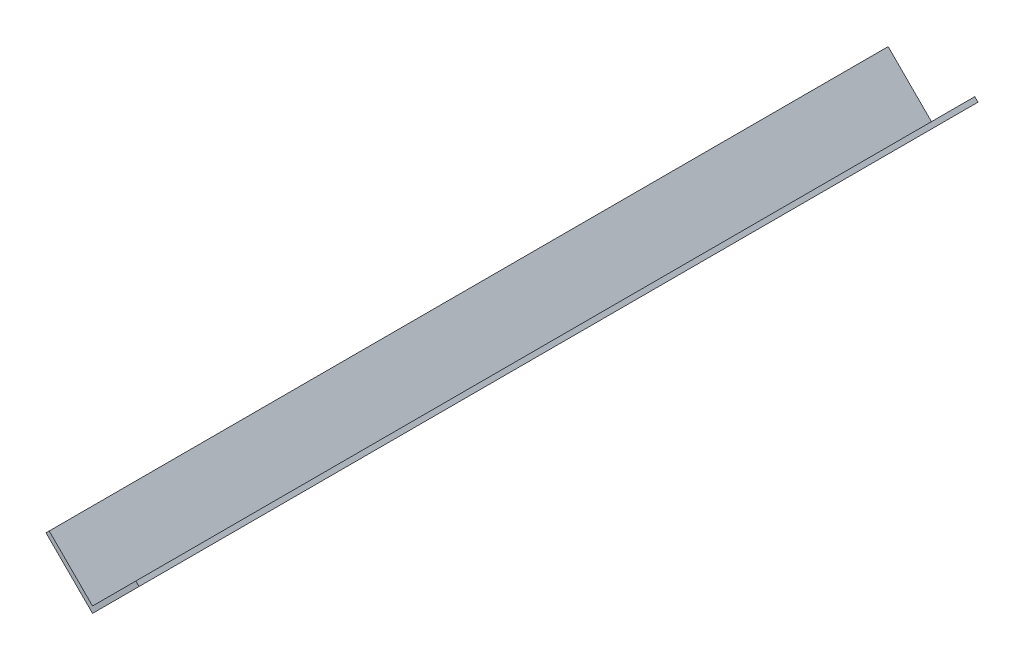
SolidWorks part; units mm, degrees
material "6061 Alloy"
ref_plane "Front Plane" through (0, 0, 0) normal (0, 0, 1) x (1, 0, 0)
ref_plane "Top Plane" through (0, 0, 0) normal (0, 1, 0) x (1, 0, 0)
ref_plane "Right Plane" through (0, 0, 0) normal (1, 0, 0) x (0, 0, -1)
sketch "Sketch1" plane through (0, 0, 0) normal (0, 0, 1) x (1, 0, 0)
  line L0 (0, 0) -> (-17.9605, 17.9605)
  line L1 (-17.9605, 17.9605) -> (-16.7257, 19.1953)
  line L2 (-16.7257, 19.1953) -> (0, 2.4696)
  line L3 (0, 2.4696) -> (16.7257, 19.1953)
  line L4 (16.7257, 19.1953) -> (17.9605, 17.9605)
  line L5 (17.9605, 17.9605) -> (0, 0)
  dimension "D1" = 1.7463
  dimension "D2" = 25.4
extrude "Boss-Extrude1" add sketch "Sketch1" along normal blind 323.85
sketch "Sketch3" [suppressed] plane through (0, 0, 0) normal (1, 0, 0) x (0, 0, -1)
  line L0 (-276.225, 16.0203) -> (-323.85, 16.0203) construction
  line L6 (-196.85, 19.1953) -> (-203.2, 19.1953)
  line L7 (-203.2, 19.1953) -> (-203.2, 16.0203)
  line L8 (-196.85, 16.0203) -> (-196.85, 19.1953)
  line L9 (-120.65, 19.1953) -> (-127, 19.1953)
  line L10 (-127, 19.1953) -> (-127, 16.0203)
  line L11 (-120.65, 16.0203) -> (-120.65, 19.1953)
  line L16 (-44.45, 19.1953) -> (-50.8, 19.1953)
  line L17 (-50.8, 19.1953) -> (-50.8, 16.0203)
  line L22 (-44.45, 16.0203) -> (-44.45, 19.1953)
  line L28 (-323.85, 0) -> (-323.85, 17.9605) construction
  line L29 (-276.225, 16.0203) -> (-200.025, 16.0203) construction
  line L30 (-279.4, 19.1953) -> (-279.4, 16.0203)
  line L31 (-323.85, 19.1953) -> (0, 19.1953) construction
  line L32 (-273.05, 16.0203) -> (-273.05, 19.1953)
  line L33 (-273.05, 19.1953) -> (-279.4, 19.1953)
  line L34 (-200.025, 16.0203) -> (-123.825, 16.0203) construction
  line L35 (-123.825, 16.0203) -> (-47.625, 16.0203) construction
  line L36 (-47.625, 16.0203) -> (0, 16.0203) construction
  line L37 (0, 0) -> (0, 17.9605) construction
  arc A0 (-279.4, 16.0203) -> (-273.05, 16.0203) centre (-276.225, 16.0203) ccw
  arc A1 (-203.2, 16.0203) -> (-196.85, 16.0203) centre (-200.025, 16.0203) ccw
  arc A2 (-127, 16.0203) -> (-120.65, 16.0203) centre (-123.825, 16.0203) ccw
  arc A3 (-50.8, 16.0203) -> (-44.45, 16.0203) centre (-47.625, 16.0203) ccw
  dimension "D1" = 76.2
  dimension "D5" = 3.175
  dimension "D4" = 6.35
extrude "Cut-Extrude2" [suppressed] cut sketch "Sketch3" against normal through all both and the other way through all
sketch "Sketch4" [suppressed] plane through (0, 0, 0) normal (0.7071, -0.7071, 0) x (0, 0, -1)
  line L0 (-279.4, 25.4) -> (-279.4, 19.5947)
  line L1 (-273.05, 19.5947) -> (-273.05, 25.4)
  line L17 (-273.05, 25.4) -> (-279.4, 25.4)
  line L21 (-203.2, 25.4) -> (-203.2, 19.5947)
  line L22 (-196.85, 19.5947) -> (-196.85, 25.4)
  line L23 (-196.85, 25.4) -> (-203.2, 25.4)
  line L24 (-127, 25.4) -> (-127, 19.5947)
  line L25 (-120.65, 19.5947) -> (-120.65, 25.4)
  line L26 (-120.65, 25.4) -> (-127, 25.4)
  line L27 (-50.8, 25.4) -> (-50.8, 19.5947)
  line L28 (-44.45, 19.5947) -> (-44.45, 25.4)
  line L29 (-44.45, 25.4) -> (-50.8, 25.4)
  line L30 (-50.8, 22.6561) -> (-50.8, 25.4) construction
  arc A0 (-279.4, 19.5947) -> (-273.05, 19.5947) centre (-276.225, 19.5947) ccw
  arc A2 (-203.2, 19.5947) -> (-196.85, 19.5947) centre (-200.025, 19.5947) ccw
  arc A5 (-127, 19.5947) -> (-120.65, 19.5947) centre (-123.825, 19.5947) ccw
  arc A6 (-50.8, 19.5947) -> (-44.45, 19.5947) centre (-47.625, 19.5947) ccw
  ellipse E3 centre (-276.225, 20.9099) end of major axis (-276.225, 25.4) minor radius 3.175 (-279.4, 20.9099) -> (-273.05, 20.9099) ccw construction
  dimension "D1" = 4
extrude "Cut-Extrude3" [suppressed] cut sketch "Sketch4" against normal through all both and the other way through all
mirror "Mirror1" [suppressed] about plane through (0, 0, 0) normal (1, 0, 0)
